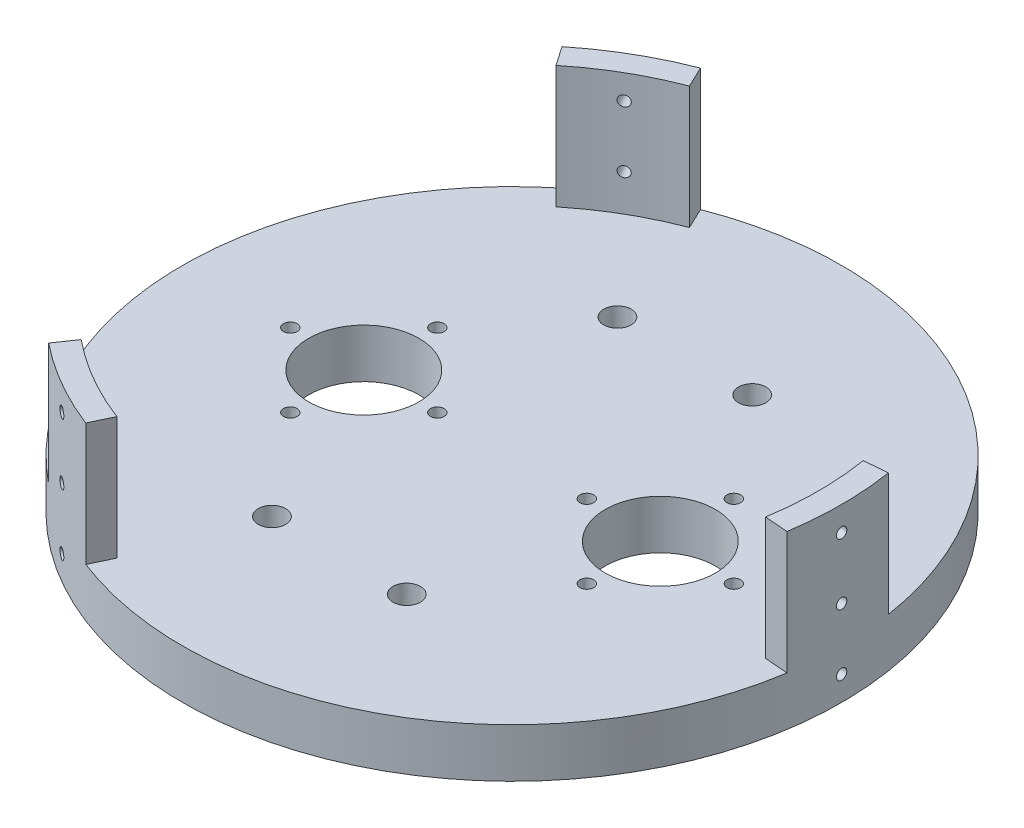
SolidWorks part; units mm, degrees
material "6061-T6 (SS)"
ref_plane "Front" through (0, 0, 0) normal (0, 0, 1) x (1, 0, 0)
ref_plane "Top" through (0, 0, 0) normal (0, 1, 0) x (1, 0, 0)
ref_plane "Right" through (0, 0, 0) normal (1, 0, 0) x (0, 0, -1)
sketch "Sketch1" plane through (0, 0, 0) normal (0, 1, 0) x (1, 0, 0)
  line L1 (0, 0) -> (127.635, 0)
  line L2 (0, 0) -> (0, 127.635)
  line L3 (0, 127.635) -> (127.635, 127.635)
  line L4 (127.635, 0) -> (127.635, 127.635)
  dimension "D1" = 127.635
  dimension "D2" = 127.635
extrude "Main Plate" add sketch "Sketch1" along normal blind 12.7
sketch "Sketch9" plane through (0, 12.7, 0) normal (0, 1, 0) x (1, 0, 0)
  circle A0 centre (63.8175, 63.8175) radius 85.725
  dimension "D1" = 171.45
extrude "Boss-Extrude1" add sketch "Sketch9" against normal up to surface (12.7 mm away) contours A0 up to face at (63.8175, 0, -63.8175)
sketch "Sketch10" plane through (0, 12.7, 0) normal (0, 1, 0) x (1, 0, 0)
  circle A0 centre (63.8175, 63.8175) radius 95.25
  circle A1 centre (63.8175, 63.8175) radius 85.4075
  dimension "D1" = 170.815
  dimension "D2" = 190.5
extrude "Cut-Extrude1" cut sketch "Sketch10" against normal blind 167.64 contours A0 | A1
sketch "Sketch14" plane through (0, 12.7, 0) normal (0, 1, 0) x (1, 0, 0)
  line L0 (201.1692, 63.8175) -> (-73.4523, 63.8175) construction
ref_plane "Plane1" through (0, 0, -63.8175) normal (0, 0, -1) x (-1, 0, 0)
ref_plane "Plane3" through (0, 6.35, 0) normal (0, 1, 0) x (1, 0, 0)
ref_plane "Plane2" through (-21.59, 0, 0) normal (-1, 0, 0) x (0, 0, 1)
sketch "Sketch18" plane through (0, 6.35, 0) normal (0, 1, 0) x (1, 0, 0)
  circle A0 centre (63.8175, 63.8175) radius 85.4075
  circle A1 centre (63.8175, 63.8175) radius 79.375
  circle A4 centre (63.8175, 63.8175) radius 85.4075 construction
  dimension "D1" = 158.75
extrude "Boss-Extrude2" add sketch "Sketch18" along normal blind 38.1
sketch "Sketch20" plane through (0, 12.7, 0) normal (0, 1, 0) x (1, 0, 0)
  line L0 (63.8175, 143.1925) -> (63.8175, -15.5575) construction
  line L1 (-15.5575, 63.8175) -> (143.1925, 63.8175) construction
  line L2 (63.8175, 63.8175) -> (-15.5575, -73.664) construction
  circle A0 centre (63.8175, 63.8175) radius 79.375 construction
  point P9 (0, 0)
  dimension "D1" = 30
ref_plane "Plane5" through (-15.5575, 12.7, 73.664) normal (-0.5, 0, 0.866) x (0.866, 0, 0.5)
sketch "Sketch15" plane through (166.2216, 0, 178.6143) normal (0.5, 0, -0.866) x (-0.866, 0, -0.5)
  line L3 (289.2754, 44.45) -> (130.5254, 44.45) construction
  line L4 (124.4929, 0) -> (295.3079, 0) construction
  line L6 (278.6412, 12.7) -> (141.1597, 12.7) construction
  circle A0 centre (209.9004, 22.225) radius 1.3526
  circle A1 centre (209.9004, 38.1) radius 1.3526
  circle A2 centre (209.9004, 6.35) radius 1.3526
  point P10 (0, 0)
  point P11 (0, 0)
  point P16 (209.9004, 12.7)
  point P17 (0, 0)
  point P18 (0, 0)
  point P19 (0, 0)
  dimension "D1" = 2.7051
  dimension "D2" = 15.875
  dimension "D3" = 2.7051
  dimension "D4" = 2.7051
  dimension "D5" = 6.35
  dimension "D6" = 6.35
  dimension "D7" = 0
extrude "Cut-Extrude3" cut sketch "Sketch15" along normal blind 88.9
pattern_circular "CirPattern1" count 3 over 360 about axis through (63.8175, -154.94, -63.8175) along (0, 1, 0) of "Cut-Extrude3" reverse direction yes
ref_plane "Plane4" through (63.8175, 0, 0) normal (-1, 0, 0) x (0, 0, 1)
sketch "Sketch21" plane through (0, 12.7, 0) normal (0, 1, 0) x (1, 0, 0)
  line L1 (-15.5575, 63.8175) -> (143.1925, 63.8175) construction
  line L2 (102.235, 63.8175) -> (102.235, 100.651) construction
  line L3 (63.8175, 87.3125) -> (63.8175, -87.3125) construction
  circle A0 centre (102.235, 63.8175) radius 14.2875
  circle A1 centre (102.235, 82.8675) radius 1.778
  circle A2 centre (25.4, 63.8175) radius 14.2875
  circle A3 centre (121.285, 63.8175) radius 1.778
  circle A4 centre (102.235, 44.7675) radius 1.778
  circle A5 centre (83.185, 63.8175) radius 1.778
  circle A6 centre (25.4, 82.8675) radius 1.778
  circle A7 centre (6.35, 63.8175) radius 1.778
  circle A8 centre (25.4, 44.7675) radius 1.778
  circle A9 centre (44.45, 63.8175) radius 1.778
  dimension "D1" = 28.575
  dimension "D2" = 3.556
  dimension "D6" = 19.05
  dimension "D3" = 19.05
  dimension "D4" = 76.835
  dimension "D7" = 19.05
  dimension "D5" = 4
extrude "CO2 Mounts" cut sketch "Sketch21" against normal through all
sketch "Sketch22" plane through (0, 12.7, 0) normal (0, 1, 0) x (1, 0, 0)
  line L0 (63.8175, 87.3125) -> (63.8175, -87.3125) construction
  line L1 (87.3125, 63.8175) -> (-87.3125, 63.8175) construction
  circle A0 centre (46.355, 108.585) radius 3.556
  circle A1 centre (81.28, 108.585) radius 3.556
  circle A2 centre (81.28, 19.05) radius 3.556
  circle A3 centre (46.355, 19.05) radius 3.556
  dimension "D1" = 7.112
  dimension "D2" = 34.925
  dimension "D3" = 89.535
extrude "Cut-Extrude5" cut sketch "Sketch22" against normal through all
sketch "Sketch23" plane through (0, 12.7, 0) normal (0, 1, 0) x (1, 0, 0)
  line L0 (13.6787, 125.352) -> (7.5523, 134.2379)
  line L1 (15.1867, 11.8815) -> (13.6787, 2.283) construction
  line L3 (-15.5575, 63.8175) -> (143.1925, 63.8175) construction
  line L4 (63.8175, 143.1925) -> (63.8175, -15.5575) construction
  line L5 (-15.5575, 63.8175) -> (143.1925, 63.8175)
  line L6 (63.8175, 143.1925) -> (63.8175, -15.5575)
  line L7 (13.6787, 2.283) -> (6.9592, -7.4631)
  line L8 (-19.2671, 125.3206) -> (-48.797, 60.3978)
  line L9 (-48.797, 60.3978) -> (-9.8843, 7.0525)
  line L10 (-9.8843, 7.0525) -> (6.9592, -7.4631)
  line L11 (24.1345, -4.9259) -> (13.6787, 2.283) construction
  line L14 (7.5523, 134.2379) -> (-19.2671, 125.3206)
  line L15 (24.1345, 132.5609) -> (13.6787, 125.352) construction
  line L28 (63.8175, 63.8175) -> (24.1345, -4.9259) construction
  line L29 (63.8175, 63.8175) -> (24.1345, 132.5609) construction
  line L30 (142.1773, 76.4717) -> (152.9359, 77.3344)
  line L31 (152.9359, 77.3344) -> (158.6231, 105.0193)
  line L32 (158.6231, 105.0193) -> (117.1632, 163.0543)
  line L33 (117.1632, 163.0543) -> (51.5085, 156.0277)
  line L34 (51.5085, 156.0277) -> (30.5159, 148.6985)
  line L35 (35.5964, 138.0062) -> (30.5159, 148.6985)
  line L36 (35.5964, -10.3712) -> (30.9643, -20.1198)
  line L37 (30.9643, -20.1198) -> (52.0965, -38.8874)
  line L38 (52.0965, -38.8874) -> (123.0863, -31.9996)
  line L39 (123.0863, -31.9996) -> (149.8284, 28.3723)
  line L40 (149.8284, 28.3723) -> (153.9775, 50.217)
  line L41 (142.1773, 51.1633) -> (153.9775, 50.217)
  circle A0 centre (63.8175, 63.8175) radius 79.375 construction
  arc A1 (13.6787, 2.283) -> (13.6787, 125.352) centre (63.8175, 63.8175) cw
  circle A3 centre (63.8175, 63.8175) radius 79.375
  arc A6 (35.5964, 138.0062) -> (142.1773, 76.4717) centre (63.8175, 63.8175) cw
  arc A7 (142.1773, 51.1633) -> (35.5964, -10.3712) centre (63.8175, 63.8175) cw
  circle A9 centre (63.8175, 63.8175) radius 79.375
  circle M15 centre (63.8175, 63.8175) radius 79.375
  dimension "D1" = 79.375
  dimension "D2" = 0
  dimension "D3" = 12.7
  dimension "D4" = 90
  dimension "D5" = 12.7
  dimension "D6" = 90
  dimension "D8" = 60.004
  dimension "D9" = 60.004
  dimension "D7" = 3
extrude "Cut-Extrude6" cut sketch "Sketch23" along normal blind 111.6 contours L9 L10 L7 L8 M15 | L34 L35 A6 L30 L31 L32 L33 | L40 L41 A7 L36 L37 L38 L39 region at (-18.2379, 12.7, -69.3048)
